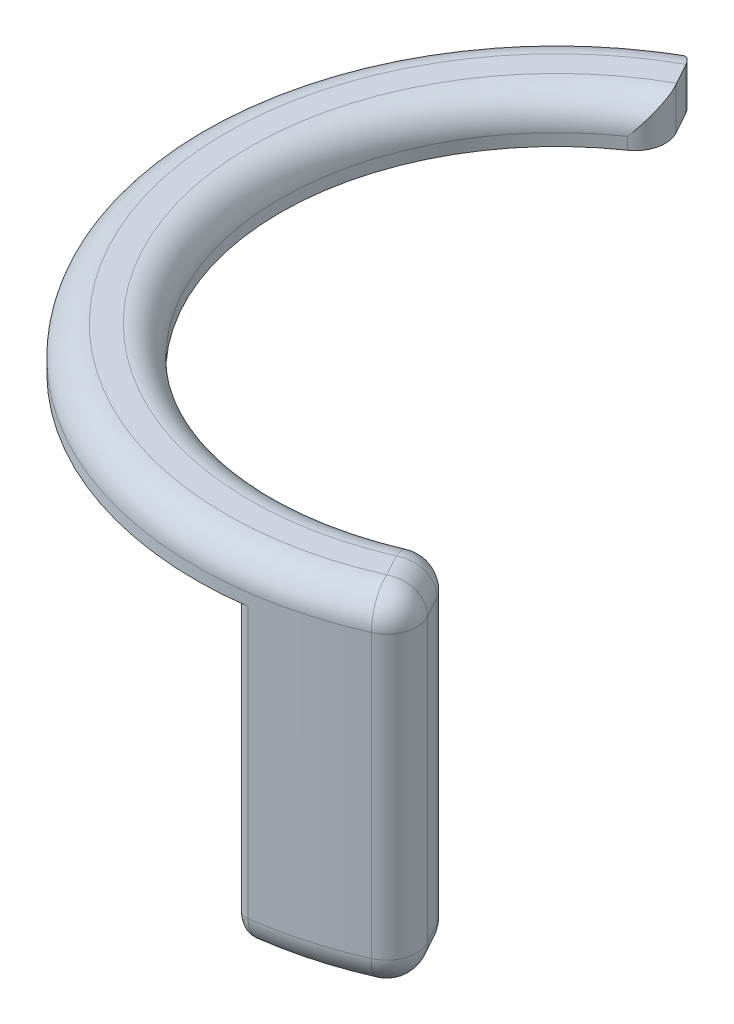
SolidWorks part; units mm, degrees
ref_plane "Front Plane" through (0, 0, 0) normal (0, 0, 1) x (1, 0, 0)
ref_plane "Top Plane" through (0, 0, 0) normal (0, 1, 0) x (1, 0, 0)
ref_plane "Right Plane" through (0, 0, 0) normal (1, 0, 0) x (0, 0, -1)
sketch "Sketch1" plane through (0, 0, 0) normal (0, 1, 0) x (1, 0, 0)
  arc A1 (14.5024, -26.2618) -> (-14.5024, 26.2618) centre (0, 0) cw
  point P2 (6.9197, 42.2613)
  point P3 (0, 0)
  point P4 (0, 0)
  dimension "D1" = 30
  dimension "D2" = 60
extrude "Extrude-Thin1" add sketch "Sketch1" along normal blind 28.5 thin thin type one direction wall 7
fillet "Fillet1" radius 2.5 10 edges at (-11.1185, 14.25, -20.134) (-14.5024, 14.25, -26.2618) (-20.134, 28.5, 11.1185) (-26.2618, 28.5, 14.5024) (14.5024, 14.25, 26.2618) (11.1185, 14.25, 20.134) (12.8105, 28.5, 23.1979) (12.8105, 0, 23.1979) (-26.2618, 0, 14.5024) (-20.134, 0, 11.1185)
sketch "Sketch2" plane through (0, 0, 0) normal (0, -1, 0) x (1, 0, 0)
  line L32 (0, 0) -> (4.2579, 41.9706)
  line L33 (4.2579, 41.9706) -> (-45.1905, 20.6909)
  line L34 (-45.1905, 20.6909) -> (-19.7846, -38.3457)
  line L35 (-19.7846, -38.3457) -> (0, 0)
  point P3 (0, 0)
  point P5 (0, 0)
  point P6 (0, 0)
  point P7 (-24.2872, -28.8511)
  point P8 (-17.6309, -34.1716)
extrude "Cut-Extrude1" cut sketch "Sketch2" against normal blind 25
fillet "Fillet3" radius 1 5 edges at (2.3214, 13.75, 22.8825) (2.3953, 0.7322, 23.611) (3.0279, 13.75, 29.8468) (2.954, 0.7322, 29.1183) (2.6747, 0, 26.3647)
sketch "Sketch3" plane through (0, 0, 0) normal (0, -1, 0) x (1, 0, 0)
  line L0 (27.5, 0) -> (23.5, 0) construction
  circle A0 centre (26.0622, 3.5) radius 2.25
  dimension "D1" = 4.5
  dimension "D2" = 3.5
extrude "Cut-Extrude2" cut sketch "Sketch3" against normal blind 2.55 rebuild error yes
